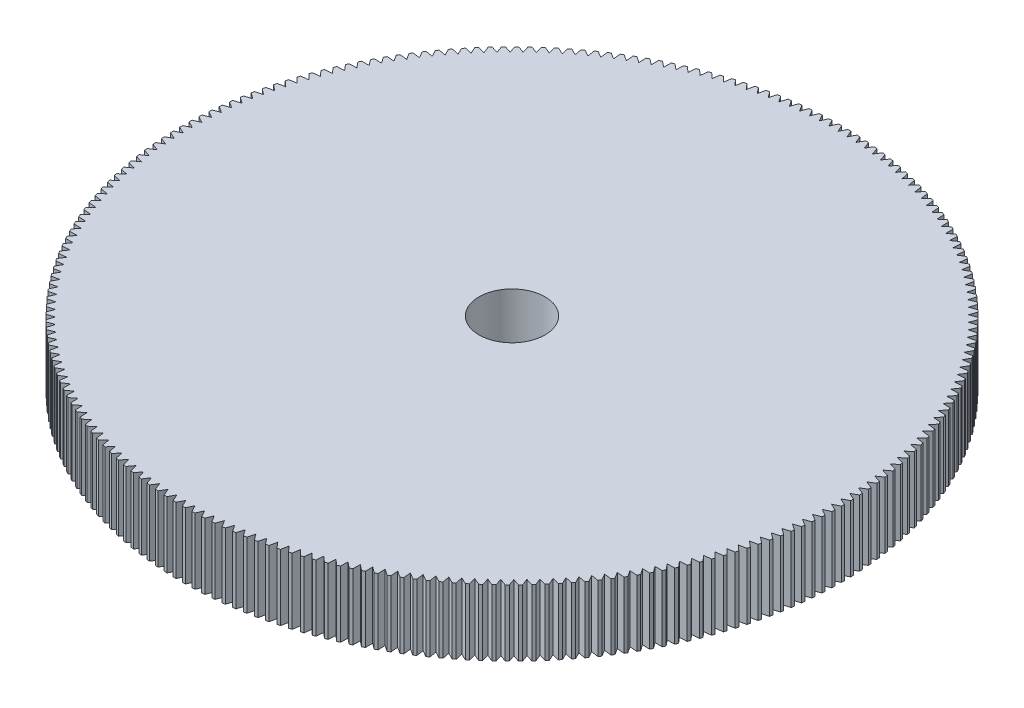
SolidWorks part; units mm, degrees
ref_plane "Ön Düzlem" through (0, 0, 0) normal (0, 0, 1) x (1, 0, 0)
ref_plane "Üst Düzlem" through (0, 0, 0) normal (0, 1, 0) x (1, 0, 0)
ref_plane "Sağ Düzlem" through (0, 0, 0) normal (1, 0, 0) x (0, 0, -1)
sketch "Çizim2" plane through (0, 0, 0) normal (0, 1, 0) x (1, 0, 0)
  line L0 (-15.8179, 18.6337) -> (-15.9533, 19.1731)
  line L1 (-16.328, 18.8549) -> (-15.8179, 18.6337)
  line L2 (-15.2793, 19.0778) -> (-15.3993, 19.6208)
  line L3 (-15.783, 19.3135) -> (-15.2793, 19.0778)
  line L4 (-14.7283, 19.5064) -> (-14.8327, 20.0525)
  line L5 (-15.225, 19.7563) -> (-14.7283, 19.5064)
  line L6 (-14.1653, 19.919) -> (-14.254, 20.4679)
  line L7 (-14.6546, 20.183) -> (-14.1653, 19.919)
  line L8 (-13.5907, 20.3154) -> (-13.6637, 20.8666)
  line L9 (-14.0723, 20.5933) -> (-13.5907, 20.3154)
  line L10 (-13.005, 20.6952) -> (-13.0623, 21.2483)
  line L11 (-13.4785, 20.9867) -> (-13.005, 20.6952)
  line L12 (-12.4087, 21.0581) -> (-12.4502, 21.6126)
  line L13 (-12.8737, 21.3631) -> (-12.4087, 21.0581)
  line L14 (-11.8023, 21.4039) -> (-11.8279, 21.9593)
  line L15 (-12.2584, 21.722) -> (-11.8023, 21.4039)
  line L16 (-11.1863, 21.7322) -> (-11.196, 22.2882)
  line L17 (-11.6331, 22.0632) -> (-11.1863, 21.7322)
  line L18 (-10.5612, 22.0427) -> (-10.555, 22.5988)
  line L19 (-10.9984, 22.3864) -> (-10.5612, 22.0427)
  line L20 (-9.9274, 22.3353) -> (-9.9054, 22.891)
  line L21 (-10.3546, 22.6913) -> (-9.9274, 22.3353)
  line L22 (-9.2855, 22.6097) -> (-9.2477, 23.1645)
  line L23 (-9.7024, 22.9777) -> (-9.2855, 22.6097)
  line L24 (-8.6361, 22.8657) -> (-8.5824, 23.4191)
  line L25 (-9.0423, 23.2454) -> (-8.6361, 22.8657)
  line L26 (-7.9796, 23.1029) -> (-7.9101, 23.6547)
  line L27 (-8.3748, 23.4942) -> (-7.9796, 23.1029)
  line L28 (-7.3167, 23.3214) -> (-7.2314, 23.8709)
  line L29 (-7.7005, 23.7237) -> (-7.3167, 23.3214)
  line L30 (-6.6477, 23.5208) -> (-6.5468, 24.0677)
  line L31 (-7.0199, 23.9339) -> (-6.6477, 23.5208)
  line L32 (-5.9733, 23.7011) -> (-5.8569, 24.2448)
  line L33 (-6.3336, 24.1246) -> (-5.9733, 23.7011)
  line L34 (-5.2941, 23.862) -> (-5.1622, 24.4022)
  line L35 (-5.6421, 24.2957) -> (-5.2941, 23.862)
  line L36 (-4.6105, 24.0034) -> (-4.4632, 24.5396)
  line L37 (-4.946, 24.4469) -> (-4.6105, 24.0034)
  line L38 (-3.9232, 24.1253) -> (-3.7606, 24.6571)
  line L39 (-4.2459, 24.5781) -> (-3.9232, 24.1253)
  line L40 (-3.2327, 24.2275) -> (-3.055, 24.7544)
  line L41 (-3.5423, 24.6894) -> (-3.2327, 24.2275)
  line L42 (-2.5395, 24.3099) -> (-2.3469, 24.8315)
  line L43 (-2.8358, 24.7805) -> (-2.5395, 24.3099)
  line L44 (-1.8443, 24.3725) -> (-1.6368, 24.8884)
  line L45 (-2.127, 24.8513) -> (-1.8443, 24.3725)
  line L46 (-1.1476, 24.4152) -> (-0.9254, 24.925)
  line L47 (-1.4165, 24.9019) -> (-1.1476, 24.4152)
  line L48 (-0.4499, 24.4381) -> (-0.2133, 24.9413)
  line L49 (-0.7048, 24.9322) -> (-0.4499, 24.4381)
  line L50 (0.2482, 24.4409) -> (0.499, 24.9372)
  line L51 (0.0074, 24.9422) -> (0.2482, 24.4409)
  line L52 (0.946, 24.4239) -> (1.2109, 24.9128)
  line L53 (0.7197, 24.9318) -> (0.946, 24.4239)
  line L54 (1.6431, 24.3869) -> (1.9218, 24.868)
  line L55 (1.4313, 24.9011) -> (1.6431, 24.3869)
  line L56 (2.3388, 24.33) -> (2.6312, 24.803)
  line L57 (2.1418, 24.8501) -> (2.3388, 24.33)
  line L58 (3.0326, 24.2533) -> (3.3384, 24.7178)
  line L59 (2.8506, 24.7788) -> (3.0326, 24.2533)
  line L60 (3.7239, 24.1568) -> (4.0429, 24.6124)
  line L61 (3.557, 24.6873) -> (3.7239, 24.1568)
  line L62 (4.4122, 24.0406) -> (4.744, 24.4869)
  line L63 (4.2605, 24.5756) -> (4.4122, 24.0406)
  line L64 (5.0969, 23.9048) -> (5.4414, 24.3414)
  line L65 (4.9606, 24.4439) -> (5.0969, 23.9048)
  line L66 (5.7775, 23.7496) -> (6.1342, 24.1761)
  line L67 (5.6566, 24.2923) -> (5.7775, 23.7496)
  line L68 (6.4533, 23.5749) -> (6.8221, 23.9911)
  line L69 (6.3479, 24.1209) -> (6.4533, 23.5749)
  line L70 (7.1239, 23.381) -> (7.5044, 23.7865)
  line L71 (7.0342, 23.9298) -> (7.1239, 23.381)
  line L72 (7.7887, 23.168) -> (8.1806, 23.5625)
  line L73 (7.7146, 23.7191) -> (7.7887, 23.168)
  line L74 (8.4471, 22.9362) -> (8.8501, 23.3193)
  line L75 (8.3888, 23.4892) -> (8.4471, 22.9362)
  line L76 (9.0986, 22.6856) -> (9.5124, 23.057)
  line L77 (9.0561, 23.24) -> (9.0986, 22.6856)
  line L78 (9.7427, 22.4165) -> (10.167, 22.776)
  line L79 (9.7161, 22.9719) -> (9.7427, 22.4165)
  line L80 (10.3789, 22.1292) -> (10.8132, 22.4764)
  line L81 (10.3681, 22.6851) -> (10.3789, 22.1292)
  line L82 (11.0065, 21.8238) -> (11.4506, 22.1584)
  line L83 (11.0117, 22.3798) -> (11.0065, 21.8238)
  line L84 (11.6253, 21.5006) -> (12.0787, 21.8224)
  line L85 (11.6463, 22.0562) -> (11.6253, 21.5006)
  line L86 (12.2345, 21.1598) -> (12.697, 21.4686)
  line L87 (12.2714, 21.7147) -> (12.2345, 21.1598)
  line L88 (12.8337, 20.8018) -> (13.3048, 21.0973)
  line L89 (12.8864, 21.3554) -> (12.8337, 20.8018)
  line L90 (13.4225, 20.4269) -> (13.9019, 20.7087)
  line L91 (13.491, 20.9787) -> (13.4225, 20.4269)
  line L92 (14.0004, 20.0352) -> (14.4876, 20.3033)
  line L93 (14.0846, 20.5849) -> (14.0004, 20.0352)
  line L94 (14.5668, 19.6273) -> (15.0614, 19.8813)
  line L95 (14.6667, 20.1743) -> (14.5668, 19.6273)
  line L96 (15.1213, 19.2033) -> (15.623, 19.4431)
  line L97 (15.2368, 19.7472) -> (15.1213, 19.2033)
  line L98 (15.6635, 18.7637) -> (16.1719, 18.989)
  line L99 (15.7945, 19.3041) -> (15.6635, 18.7637)
  line L100 (16.1929, 18.3087) -> (16.7075, 18.5195)
  line L101 (16.3393, 18.8452) -> (16.1929, 18.3087)
  line L102 (16.7092, 17.8388) -> (17.2295, 18.0348)
  line L103 (16.8708, 18.3709) -> (16.7092, 17.8388)
  line L104 (17.2118, 17.3544) -> (17.7375, 17.5355)
  line L105 (17.3885, 17.8817) -> (17.2118, 17.3544)
  line L106 (17.7003, 16.8558) -> (18.231, 17.0218)
  line L107 (17.892, 17.3778) -> (17.7003, 16.8558)
  line L108 (18.1744, 16.3435) -> (18.7097, 16.4943)
  line L109 (18.381, 16.8598) -> (18.1744, 16.3435)
  line L110 (18.6337, 15.8179) -> (19.1731, 15.9533)
  line L111 (18.8549, 16.328) -> (18.6337, 15.8179)
  line L112 (19.0778, 15.2793) -> (19.6208, 15.3993)
  line L113 (19.3135, 15.783) -> (19.0778, 15.2793)
  line L114 (19.5064, 14.7283) -> (20.0525, 14.8327)
  line L115 (19.7563, 15.225) -> (19.5064, 14.7283)
  line L116 (19.919, 14.1653) -> (20.4679, 14.254)
  line L117 (20.183, 14.6546) -> (19.919, 14.1653)
  line L118 (20.3154, 13.5907) -> (20.8666, 13.6637)
  line L119 (20.5933, 14.0723) -> (20.3154, 13.5907)
  line L120 (20.6952, 13.005) -> (21.2483, 13.0623)
  line L121 (20.9867, 13.4785) -> (20.6952, 13.005)
  line L122 (21.0581, 12.4087) -> (21.6126, 12.4502)
  line L123 (21.3631, 12.8737) -> (21.0581, 12.4087)
  line L124 (21.4039, 11.8023) -> (21.9593, 11.8279)
  line L125 (21.722, 12.2584) -> (21.4039, 11.8023)
  line L126 (21.7322, 11.1863) -> (22.2882, 11.196)
  line L127 (22.0632, 11.6331) -> (21.7322, 11.1863)
  line L128 (22.0427, 10.5612) -> (22.5988, 10.555)
  line L129 (22.3864, 10.9984) -> (22.0427, 10.5612)
  line L130 (22.3353, 9.9274) -> (22.891, 9.9054)
  line L131 (22.6913, 10.3546) -> (22.3353, 9.9274)
  line L132 (22.6097, 9.2855) -> (23.1645, 9.2477)
  line L133 (22.9777, 9.7024) -> (22.6097, 9.2855)
  line L134 (22.8657, 8.6361) -> (23.4191, 8.5824)
  line L135 (23.2454, 9.0423) -> (22.8657, 8.6361)
  line L136 (23.1029, 7.9796) -> (23.6547, 7.9101)
  line L137 (23.4942, 8.3748) -> (23.1029, 7.9796)
  line L138 (23.3214, 7.3167) -> (23.8709, 7.2314)
  line L139 (23.7237, 7.7005) -> (23.3214, 7.3167)
  line L140 (23.5208, 6.6477) -> (24.0677, 6.5468)
  line L141 (23.9339, 7.0199) -> (23.5208, 6.6477)
  line L142 (23.7011, 5.9733) -> (24.2448, 5.8569)
  line L143 (24.1246, 6.3336) -> (23.7011, 5.9733)
  line L144 (23.862, 5.2941) -> (24.4022, 5.1622)
  line L145 (24.2957, 5.6421) -> (23.862, 5.2941)
  line L146 (24.0034, 4.6105) -> (24.5396, 4.4632)
  line L147 (24.4469, 4.946) -> (24.0034, 4.6105)
  line L148 (24.1253, 3.9232) -> (24.6571, 3.7606)
  line L149 (24.5781, 4.2459) -> (24.1253, 3.9232)
  line L150 (24.2275, 3.2327) -> (24.7544, 3.055)
  line L151 (24.6894, 3.5423) -> (24.2275, 3.2327)
  line L152 (24.3099, 2.5395) -> (24.8315, 2.3469)
  line L153 (24.7805, 2.8358) -> (24.3099, 2.5395)
  line L154 (24.3725, 1.8443) -> (24.8884, 1.6368)
  line L155 (24.8513, 2.127) -> (24.3725, 1.8443)
  line L156 (24.4152, 1.1476) -> (24.925, 0.9254)
  line L157 (24.9019, 1.4165) -> (24.4152, 1.1476)
  line L158 (24.4381, 0.4499) -> (24.9413, 0.2133)
  line L159 (24.9322, 0.7048) -> (24.4381, 0.4499)
  line L160 (24.4409, -0.2482) -> (24.9372, -0.499)
  line L161 (24.9422, -0.0074) -> (24.4409, -0.2482)
  line L162 (24.4239, -0.946) -> (24.9128, -1.2109)
  line L163 (24.9318, -0.7197) -> (24.4239, -0.946)
  line L164 (24.3869, -1.6431) -> (24.868, -1.9218)
  line L165 (24.9011, -1.4313) -> (24.3869, -1.6431)
  line L166 (24.33, -2.3388) -> (24.803, -2.6312)
  line L167 (24.8501, -2.1418) -> (24.33, -2.3388)
  line L168 (24.2533, -3.0326) -> (24.7178, -3.3384)
  line L169 (24.7788, -2.8506) -> (24.2533, -3.0326)
  line L170 (24.1568, -3.7239) -> (24.6124, -4.0429)
  line L171 (24.6873, -3.557) -> (24.1568, -3.7239)
  line L172 (24.0406, -4.4122) -> (24.4869, -4.744)
  line L173 (24.5756, -4.2605) -> (24.0406, -4.4122)
  line L174 (23.9048, -5.0969) -> (24.3414, -5.4414)
  line L175 (24.4439, -4.9606) -> (23.9048, -5.0969)
  line L176 (23.7496, -5.7775) -> (24.1761, -6.1342)
  line L177 (24.2923, -5.6566) -> (23.7496, -5.7775)
  line L178 (23.5749, -6.4533) -> (23.9911, -6.8221)
  line L179 (24.1209, -6.3479) -> (23.5749, -6.4533)
  line L180 (23.381, -7.1239) -> (23.7865, -7.5044)
  line L181 (23.9298, -7.0342) -> (23.381, -7.1239)
  line L182 (23.168, -7.7887) -> (23.5625, -8.1806)
  line L183 (23.7191, -7.7146) -> (23.168, -7.7887)
  line L184 (22.9362, -8.4471) -> (23.3193, -8.8501)
  line L185 (23.4892, -8.3888) -> (22.9362, -8.4471)
  line L186 (22.6856, -9.0986) -> (23.057, -9.5124)
  line L187 (23.24, -9.0561) -> (22.6856, -9.0986)
  line L188 (22.4165, -9.7427) -> (22.776, -10.167)
  line L189 (22.9719, -9.7161) -> (22.4165, -9.7427)
  line L190 (22.1292, -10.3789) -> (22.4764, -10.8132)
  line L191 (22.6851, -10.3681) -> (22.1292, -10.3789)
  line L192 (21.8238, -11.0065) -> (22.1584, -11.4506)
  line L193 (22.3798, -11.0117) -> (21.8238, -11.0065)
  line L194 (21.5006, -11.6253) -> (21.8224, -12.0787)
  line L195 (22.0562, -11.6463) -> (21.5006, -11.6253)
  line L196 (21.1598, -12.2345) -> (21.4686, -12.697)
  line L197 (21.7147, -12.2714) -> (21.1598, -12.2345)
  line L198 (20.8018, -12.8337) -> (21.0973, -13.3048)
  line L199 (21.3554, -12.8864) -> (20.8018, -12.8337)
  line L200 (20.4269, -13.4225) -> (20.7087, -13.9019)
  line L201 (20.9787, -13.491) -> (20.4269, -13.4225)
  line L202 (20.0352, -14.0004) -> (20.3033, -14.4876)
  line L203 (20.5849, -14.0846) -> (20.0352, -14.0004)
  line L204 (19.6273, -14.5668) -> (19.8813, -15.0614)
  line L205 (20.1743, -14.6667) -> (19.6273, -14.5668)
  line L206 (19.2033, -15.1213) -> (19.4431, -15.623)
  line L207 (19.7472, -15.2368) -> (19.2033, -15.1213)
  line L208 (18.7637, -15.6635) -> (18.989, -16.1719)
  line L209 (19.3041, -15.7945) -> (18.7637, -15.6635)
  line L210 (18.3087, -16.1929) -> (18.5195, -16.7075)
  line L211 (18.8452, -16.3393) -> (18.3087, -16.1929)
  line L212 (17.8388, -16.7092) -> (18.0348, -17.2295)
  line L213 (18.3709, -16.8708) -> (17.8388, -16.7092)
  line L214 (17.3544, -17.2118) -> (17.5355, -17.7375)
  line L215 (17.8817, -17.3885) -> (17.3544, -17.2118)
  line L216 (16.8558, -17.7003) -> (17.0218, -18.231)
  line L217 (17.3778, -17.892) -> (16.8558, -17.7003)
  line L218 (16.3435, -18.1744) -> (16.4943, -18.7097)
  line L219 (16.8598, -18.381) -> (16.3435, -18.1744)
  line L220 (15.8179, -18.6337) -> (15.9533, -19.1731)
  line L221 (16.328, -18.8549) -> (15.8179, -18.6337)
  line L222 (15.2793, -19.0778) -> (15.3993, -19.6208)
  line L223 (15.783, -19.3135) -> (15.2793, -19.0778)
  line L224 (14.7283, -19.5064) -> (14.8327, -20.0525)
  line L225 (15.225, -19.7563) -> (14.7283, -19.5064)
  line L226 (14.1653, -19.919) -> (14.254, -20.4679)
  line L227 (14.6546, -20.183) -> (14.1653, -19.919)
  line L228 (13.5907, -20.3154) -> (13.6637, -20.8666)
  line L229 (14.0723, -20.5933) -> (13.5907, -20.3154)
  line L230 (13.005, -20.6952) -> (13.0623, -21.2483)
  line L231 (13.4785, -20.9867) -> (13.005, -20.6952)
  line L232 (12.4087, -21.0581) -> (12.4502, -21.6126)
  line L233 (12.8737, -21.3631) -> (12.4087, -21.0581)
  line L234 (11.8023, -21.4039) -> (11.8279, -21.9593)
  line L235 (12.2584, -21.722) -> (11.8023, -21.4039)
  line L236 (11.1863, -21.7322) -> (11.196, -22.2882)
  line L237 (11.6331, -22.0632) -> (11.1863, -21.7322)
  line L238 (10.5612, -22.0427) -> (10.555, -22.5988)
  line L239 (10.9984, -22.3864) -> (10.5612, -22.0427)
  line L240 (9.9274, -22.3353) -> (9.9054, -22.891)
  line L241 (10.3546, -22.6913) -> (9.9274, -22.3353)
  line L242 (9.2855, -22.6097) -> (9.2477, -23.1645)
  line L243 (9.7024, -22.9777) -> (9.2855, -22.6097)
  line L244 (8.6361, -22.8657) -> (8.5824, -23.4191)
  line L245 (9.0423, -23.2454) -> (8.6361, -22.8657)
  line L246 (7.9796, -23.1029) -> (7.9101, -23.6547)
  line L247 (8.3748, -23.4942) -> (7.9796, -23.1029)
  line L248 (7.3167, -23.3214) -> (7.2314, -23.8709)
  line L249 (7.7005, -23.7237) -> (7.3167, -23.3214)
  line L250 (6.6477, -23.5208) -> (6.5468, -24.0677)
  line L251 (7.0199, -23.9339) -> (6.6477, -23.5208)
  line L252 (5.9733, -23.7011) -> (5.8569, -24.2448)
  line L253 (6.3336, -24.1246) -> (5.9733, -23.7011)
  line L254 (5.2941, -23.862) -> (5.1622, -24.4022)
  line L255 (5.6421, -24.2957) -> (5.2941, -23.862)
  line L256 (4.6105, -24.0034) -> (4.4632, -24.5396)
  line L257 (4.946, -24.4469) -> (4.6105, -24.0034)
  line L258 (3.9232, -24.1253) -> (3.7606, -24.6571)
  line L259 (4.2459, -24.5781) -> (3.9232, -24.1253)
  line L260 (3.2327, -24.2275) -> (3.055, -24.7544)
  line L261 (3.5423, -24.6894) -> (3.2327, -24.2275)
  line L262 (2.5395, -24.3099) -> (2.3469, -24.8315)
  line L263 (2.8358, -24.7805) -> (2.5395, -24.3099)
  line L264 (1.8443, -24.3725) -> (1.6368, -24.8884)
  line L265 (2.127, -24.8513) -> (1.8443, -24.3725)
  line L266 (1.1476, -24.4152) -> (0.9254, -24.925)
  line L267 (1.4165, -24.9019) -> (1.1476, -24.4152)
  line L268 (0.4499, -24.4381) -> (0.2133, -24.9413)
  line L269 (0.7048, -24.9322) -> (0.4499, -24.4381)
  line L270 (-0.2482, -24.4409) -> (-0.499, -24.9372)
  line L271 (-0.0074, -24.9422) -> (-0.2482, -24.4409)
  line L272 (-0.946, -24.4239) -> (-1.2109, -24.9128)
  line L273 (-0.7197, -24.9318) -> (-0.946, -24.4239)
  line L274 (-1.6431, -24.3869) -> (-1.9218, -24.868)
  line L275 (-1.4313, -24.9011) -> (-1.6431, -24.3869)
  line L276 (-2.3388, -24.33) -> (-2.6312, -24.803)
  line L277 (-2.1418, -24.8501) -> (-2.3388, -24.33)
  line L278 (-3.0326, -24.2533) -> (-3.3384, -24.7178)
  line L279 (-2.8506, -24.7788) -> (-3.0326, -24.2533)
  line L280 (-3.7239, -24.1568) -> (-4.0429, -24.6124)
  line L281 (-3.557, -24.6873) -> (-3.7239, -24.1568)
  line L282 (-4.4122, -24.0406) -> (-4.744, -24.4869)
  line L283 (-4.2605, -24.5756) -> (-4.4122, -24.0406)
  line L284 (-5.0969, -23.9048) -> (-5.4414, -24.3414)
  line L285 (-4.9606, -24.4439) -> (-5.0969, -23.9048)
  line L286 (-5.7775, -23.7496) -> (-6.1342, -24.1761)
  line L287 (-5.6566, -24.2923) -> (-5.7775, -23.7496)
  line L288 (-6.4533, -23.5749) -> (-6.8221, -23.9911)
  line L289 (-6.3479, -24.1209) -> (-6.4533, -23.5749)
  line L290 (-7.1239, -23.381) -> (-7.5044, -23.7865)
  line L291 (-7.0342, -23.9298) -> (-7.1239, -23.381)
  line L292 (-7.7887, -23.168) -> (-8.1806, -23.5625)
  line L293 (-7.7146, -23.7191) -> (-7.7887, -23.168)
  line L294 (-8.4471, -22.9362) -> (-8.8501, -23.3193)
  line L295 (-8.3888, -23.4892) -> (-8.4471, -22.9362)
  line L296 (-9.0986, -22.6856) -> (-9.5124, -23.057)
  line L297 (-9.0561, -23.24) -> (-9.0986, -22.6856)
  line L298 (-9.7427, -22.4165) -> (-10.167, -22.776)
  line L299 (-9.7161, -22.9719) -> (-9.7427, -22.4165)
  line L300 (-10.3789, -22.1292) -> (-10.8132, -22.4764)
  line L301 (-10.3681, -22.6851) -> (-10.3789, -22.1292)
  line L302 (-11.0065, -21.8238) -> (-11.4506, -22.1584)
  line L303 (-11.0117, -22.3798) -> (-11.0065, -21.8238)
  line L304 (-11.6253, -21.5006) -> (-12.0787, -21.8224)
  line L305 (-11.6463, -22.0562) -> (-11.6253, -21.5006)
  line L306 (-12.2345, -21.1598) -> (-12.697, -21.4686)
  line L307 (-12.2714, -21.7147) -> (-12.2345, -21.1598)
  line L308 (-12.8337, -20.8018) -> (-13.3048, -21.0973)
  line L309 (-12.8864, -21.3554) -> (-12.8337, -20.8018)
  line L310 (-13.4225, -20.4269) -> (-13.9019, -20.7087)
  line L311 (-13.491, -20.9787) -> (-13.4225, -20.4269)
  line L312 (-14.0004, -20.0352) -> (-14.4876, -20.3033)
  line L313 (-14.0846, -20.5849) -> (-14.0004, -20.0352)
  line L314 (-14.5668, -19.6273) -> (-15.0614, -19.8813)
  line L315 (-14.6667, -20.1743) -> (-14.5668, -19.6273)
  line L316 (-15.1213, -19.2033) -> (-15.623, -19.4431)
  line L317 (-15.2368, -19.7472) -> (-15.1213, -19.2033)
  line L318 (-15.6635, -18.7637) -> (-16.1719, -18.989)
  line L319 (-15.7945, -19.3041) -> (-15.6635, -18.7637)
  line L320 (-16.1929, -18.3087) -> (-16.7075, -18.5195)
  line L321 (-16.3393, -18.8452) -> (-16.1929, -18.3087)
  line L322 (-16.7092, -17.8388) -> (-17.2295, -18.0348)
  line L323 (-16.8708, -18.3709) -> (-16.7092, -17.8388)
  line L324 (-17.2118, -17.3544) -> (-17.7375, -17.5355)
  line L325 (-17.3885, -17.8817) -> (-17.2118, -17.3544)
  line L326 (-17.7003, -16.8558) -> (-18.231, -17.0218)
  line L327 (-17.892, -17.3778) -> (-17.7003, -16.8558)
  line L328 (-18.1744, -16.3435) -> (-18.7097, -16.4943)
  line L329 (-18.381, -16.8598) -> (-18.1744, -16.3435)
  line L330 (-18.6337, -15.8179) -> (-19.1731, -15.9533)
  line L331 (-18.8549, -16.328) -> (-18.6337, -15.8179)
  line L332 (-19.0778, -15.2793) -> (-19.6208, -15.3993)
  line L333 (-19.3135, -15.783) -> (-19.0778, -15.2793)
  line L334 (-19.5064, -14.7283) -> (-20.0525, -14.8327)
  line L335 (-19.7563, -15.225) -> (-19.5064, -14.7283)
  line L336 (-19.919, -14.1653) -> (-20.4679, -14.254)
  line L337 (-20.183, -14.6546) -> (-19.919, -14.1653)
  line L338 (-20.3154, -13.5907) -> (-20.8666, -13.6637)
  line L339 (-20.5933, -14.0723) -> (-20.3154, -13.5907)
  line L340 (-20.6952, -13.005) -> (-21.2483, -13.0623)
  line L341 (-20.9867, -13.4785) -> (-20.6952, -13.005)
  line L342 (-21.0581, -12.4087) -> (-21.6126, -12.4502)
  line L343 (-21.3631, -12.8737) -> (-21.0581, -12.4087)
  line L344 (-21.4039, -11.8023) -> (-21.9593, -11.8279)
  line L345 (-21.722, -12.2584) -> (-21.4039, -11.8023)
  line L346 (-21.7322, -11.1863) -> (-22.2882, -11.196)
  line L347 (-22.0632, -11.6331) -> (-21.7322, -11.1863)
  line L348 (-22.0427, -10.5612) -> (-22.5988, -10.555)
  line L349 (-22.3864, -10.9984) -> (-22.0427, -10.5612)
  line L350 (-22.3353, -9.9274) -> (-22.891, -9.9054)
  line L351 (-22.6913, -10.3546) -> (-22.3353, -9.9274)
  line L352 (-22.6097, -9.2855) -> (-23.1645, -9.2477)
  line L353 (-22.9777, -9.7024) -> (-22.6097, -9.2855)
  line L354 (-22.8657, -8.6361) -> (-23.4191, -8.5824)
  line L355 (-23.2454, -9.0423) -> (-22.8657, -8.6361)
  line L356 (-23.1029, -7.9796) -> (-23.6547, -7.9101)
  line L357 (-23.4942, -8.3748) -> (-23.1029, -7.9796)
  line L358 (-23.3214, -7.3167) -> (-23.8709, -7.2314)
  line L359 (-23.7237, -7.7005) -> (-23.3214, -7.3167)
  line L360 (-23.5208, -6.6477) -> (-24.0677, -6.5468)
  line L361 (-23.9339, -7.0199) -> (-23.5208, -6.6477)
  line L362 (-23.7011, -5.9733) -> (-24.2448, -5.8569)
  line L363 (-24.1246, -6.3336) -> (-23.7011, -5.9733)
  line L364 (-23.862, -5.2941) -> (-24.4022, -5.1622)
  line L365 (-24.2957, -5.6421) -> (-23.862, -5.2941)
  line L366 (-24.0034, -4.6105) -> (-24.5396, -4.4632)
  line L367 (-24.4469, -4.946) -> (-24.0034, -4.6105)
  line L368 (-24.1253, -3.9232) -> (-24.6571, -3.7606)
  line L369 (-24.5781, -4.2459) -> (-24.1253, -3.9232)
  line L370 (-24.2275, -3.2327) -> (-24.7544, -3.055)
  line L371 (-24.6894, -3.5423) -> (-24.2275, -3.2327)
  line L372 (-24.3099, -2.5395) -> (-24.8315, -2.3469)
  line L373 (-24.7805, -2.8358) -> (-24.3099, -2.5395)
  line L374 (-24.3725, -1.8443) -> (-24.8884, -1.6368)
  line L375 (-24.8513, -2.127) -> (-24.3725, -1.8443)
  line L376 (-24.4152, -1.1476) -> (-24.925, -0.9254)
  line L377 (-24.9019, -1.4165) -> (-24.4152, -1.1476)
  line L378 (-24.4381, -0.4499) -> (-24.9413, -0.2133)
  line L379 (-24.9322, -0.7048) -> (-24.4381, -0.4499)
  line L380 (-24.4409, 0.2482) -> (-24.9372, 0.499)
  line L381 (-24.9422, 0.0074) -> (-24.4409, 0.2482)
  line L382 (-24.4239, 0.946) -> (-24.9128, 1.2109)
  line L383 (-24.9318, 0.7197) -> (-24.4239, 0.946)
  line L384 (-24.3869, 1.6431) -> (-24.868, 1.9218)
  line L385 (-24.9011, 1.4313) -> (-24.3869, 1.6431)
  line L386 (-24.33, 2.3388) -> (-24.803, 2.6312)
  line L387 (-24.8501, 2.1418) -> (-24.33, 2.3388)
  line L388 (-24.2533, 3.0326) -> (-24.7178, 3.3384)
  line L389 (-24.7788, 2.8506) -> (-24.2533, 3.0326)
  line L390 (-24.1568, 3.7239) -> (-24.6124, 4.0429)
  line L391 (-24.6873, 3.557) -> (-24.1568, 3.7239)
  line L392 (-24.0406, 4.4122) -> (-24.4869, 4.744)
  line L393 (-24.5756, 4.2605) -> (-24.0406, 4.4122)
  line L394 (-23.9048, 5.0969) -> (-24.3414, 5.4414)
  line L395 (-24.4439, 4.9606) -> (-23.9048, 5.0969)
  line L396 (-23.7496, 5.7775) -> (-24.1761, 6.1342)
  line L397 (-24.2923, 5.6566) -> (-23.7496, 5.7775)
  line L398 (-23.5749, 6.4533) -> (-23.9911, 6.8221)
  line L399 (-24.1209, 6.3479) -> (-23.5749, 6.4533)
  line L400 (-23.381, 7.1239) -> (-23.7865, 7.5044)
  line L401 (-23.9298, 7.0342) -> (-23.381, 7.1239)
  line L402 (-23.168, 7.7887) -> (-23.5625, 8.1806)
  line L403 (-23.7191, 7.7146) -> (-23.168, 7.7887)
  line L404 (-22.9362, 8.4471) -> (-23.3193, 8.8501)
  line L405 (-23.4892, 8.3888) -> (-22.9362, 8.4471)
  line L406 (-22.6856, 9.0986) -> (-23.057, 9.5124)
  line L407 (-23.24, 9.0561) -> (-22.6856, 9.0986)
  line L408 (-22.4165, 9.7427) -> (-22.776, 10.167)
  line L409 (-22.9719, 9.7161) -> (-22.4165, 9.7427)
  line L410 (-22.1292, 10.3789) -> (-22.4764, 10.8132)
  line L411 (-22.6851, 10.3681) -> (-22.1292, 10.3789)
  line L412 (-21.8238, 11.0065) -> (-22.1584, 11.4506)
  line L413 (-22.3798, 11.0117) -> (-21.8238, 11.0065)
  line L414 (-21.5006, 11.6253) -> (-21.8224, 12.0787)
  line L415 (-22.0562, 11.6463) -> (-21.5006, 11.6253)
  line L416 (-21.1598, 12.2345) -> (-21.4686, 12.697)
  line L417 (-21.7147, 12.2714) -> (-21.1598, 12.2345)
  line L418 (-20.8018, 12.8337) -> (-21.0973, 13.3048)
  line L419 (-21.3554, 12.8864) -> (-20.8018, 12.8337)
  line L420 (-20.4269, 13.4225) -> (-20.7087, 13.9019)
  line L421 (-20.9787, 13.491) -> (-20.4269, 13.4225)
  line L422 (-20.0352, 14.0004) -> (-20.3033, 14.4876)
  line L423 (-20.5849, 14.0846) -> (-20.0352, 14.0004)
  line L424 (-19.6273, 14.5668) -> (-19.8813, 15.0614)
  line L425 (-20.1743, 14.6667) -> (-19.6273, 14.5668)
  line L426 (-19.2033, 15.1213) -> (-19.4431, 15.623)
  line L427 (-19.7472, 15.2368) -> (-19.2033, 15.1213)
  line L428 (-18.7637, 15.6635) -> (-18.989, 16.1719)
  line L429 (-19.3041, 15.7945) -> (-18.7637, 15.6635)
  line L430 (-18.3087, 16.1929) -> (-18.5195, 16.7075)
  line L431 (-18.8452, 16.3393) -> (-18.3087, 16.1929)
  line L432 (-17.8388, 16.7092) -> (-18.0348, 17.2295)
  line L433 (-18.3709, 16.8708) -> (-17.8388, 16.7092)
  line L434 (-17.3544, 17.2118) -> (-17.5355, 17.7375)
  line L435 (-17.8817, 17.3885) -> (-17.3544, 17.2118)
  line L436 (-16.8558, 17.7003) -> (-17.0218, 18.231)
  line L437 (-17.3778, 17.892) -> (-16.8558, 17.7003)
  line L438 (-16.3435, 18.1744) -> (-16.4943, 18.7097)
  line L439 (-16.8598, 18.381) -> (-16.3435, 18.1744)
  circle A0 centre (0, 0) radius 24.9422
  point P667 (0, 0)
  dimension "D2" = 0.5561
  dimension "D3" = 220
extrude "Yükseklik-Ekstrüzyon3" add sketch "Çizim2" along normal blind 5 contours L269 A0 L266 L267 L264 L265 L262 L263 L260 L261 L258 L259 L256 L257 L254 L255 L252 L253 L250 L251 L248 L249 L246 L247 L244 L245 L242 L243 L240 L241 L238 L239 L236 L237 L234 region at (0, 0, 0)
sketch "Çizim3" plane through (0, 5, 0) normal (0, 1, 0) x (1, 0, 0)
  circle A0 centre (0, 0) radius 2.5
  dimension "D1" = 5
extrude "Kes-Ekstrüzyon1" cut sketch "Çizim3" against normal blind 10
